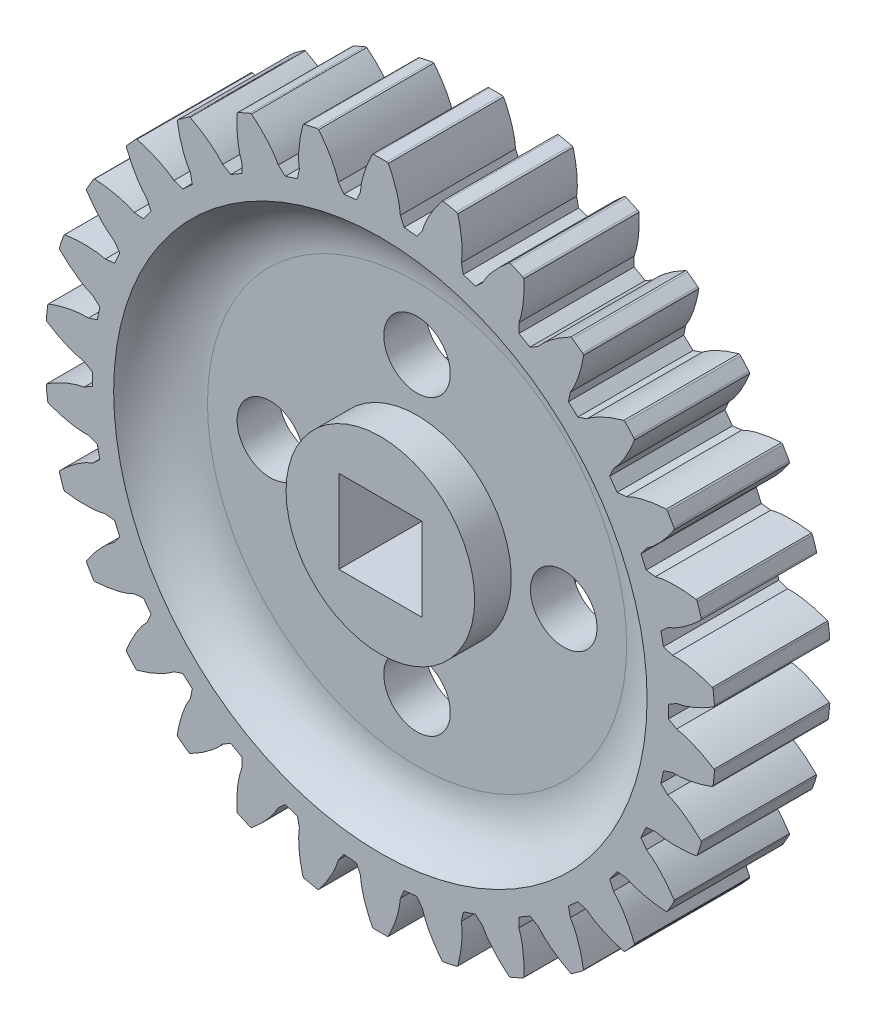
SolidWorks part; units mm, degrees
material "Nylon 101"
ref_plane "Front Plane" through (0, 0, 0) normal (0, 0, 1) x (1, 0, 0)
ref_plane "Top Plane" through (0, 0, 0) normal (0, 1, 0) x (1, 0, 0)
ref_plane "Right Plane" through (0, 0, 0) normal (1, 0, 0) x (0, 0, -1)
ref_axis "Axis1" through (0, 0, -3.2875) along (0, 0, 1)
sketch "Sketch1" plane through (0, 0, 0) normal (0, 0, 1) x (1, 0, 0)
  arc A0 (3.6196, 15.5852) -> (3.0324, 15.71) centre (0, 0) ccw
  arc A1 (0.3001, 15.9972) -> (-0.3001, 15.9972) centre (0, 0) ccw
  arc A2 (-3.0324, 15.71) -> (-3.6196, 15.5852) centre (0, 0) ccw
  arc A3 (-6.2325, 14.7362) -> (-6.7808, 14.4921) centre (0, 0) ccw
  arc A4 (-9.1601, 13.1184) -> (-9.6457, 12.7656) centre (0, 0) ccw
  arc A5 (-11.6874, 10.9272) -> (-12.089, 10.4812) centre (0, 0) ccw
  arc A6 (-13.7039, 8.2585) -> (-14.004, 7.7387) centre (0, 0) ccw
  arc A7 (-15.1215, 5.2288) -> (-15.307, 4.658) centre (0, 0) ccw
  arc A8 (-15.8782, 1.9706) -> (-15.9409, 1.3737) centre (0, 0) ccw
  arc A9 (-15.9409, -1.3737) -> (-15.8782, -1.9706) centre (0, 0) ccw
  arc A10 (-15.307, -4.658) -> (-15.1215, -5.2288) centre (0, 0) ccw
  arc A11 (-14.004, -7.7387) -> (-13.7039, -8.2585) centre (0, 0) ccw
  arc A12 (-12.089, -10.4812) -> (-11.6874, -10.9272) centre (0, 0) ccw
  arc A13 (-9.6457, -12.7656) -> (-9.1601, -13.1184) centre (0, 0) ccw
  arc A14 (-6.7808, -14.4921) -> (-6.2325, -14.7362) centre (0, 0) ccw
  arc A15 (-3.6196, -15.5852) -> (-3.0324, -15.71) centre (0, 0) ccw
  arc A16 (-0.3001, -15.9972) -> (0.3001, -15.9972) centre (0, 0) ccw
  arc A17 (3.0324, -15.71) -> (3.6196, -15.5852) centre (0, 0) ccw
  arc A18 (6.2325, -14.7362) -> (6.7808, -14.4921) centre (0, 0) ccw
  arc A19 (9.1601, -13.1184) -> (9.6457, -12.7656) centre (0, 0) ccw
  arc A20 (11.6874, -10.9272) -> (12.089, -10.4812) centre (0, 0) ccw
  arc A21 (13.7039, -8.2585) -> (14.004, -7.7387) centre (0, 0) ccw
  arc A22 (15.1215, -5.2288) -> (15.307, -4.658) centre (0, 0) ccw
  arc A23 (15.8782, -1.9706) -> (15.9409, -1.3737) centre (0, 0) ccw
  arc A24 (15.9409, 1.3737) -> (15.8782, 1.9706) centre (0, 0) ccw
  arc A25 (15.307, 4.658) -> (15.1215, 5.2288) centre (0, 0) ccw
  arc A26 (14.004, 7.7387) -> (13.7039, 8.2585) centre (0, 0) ccw
  arc A27 (12.089, 10.4812) -> (11.6874, 10.9272) centre (0, 0) ccw
  arc A28 (9.6457, 12.7656) -> (9.1601, 13.1184) centre (0, 0) ccw
  arc A29 (6.7808, 14.4921) -> (6.2325, 14.7362) centre (0, 0) ccw
  spline S0 degree 2 poles (3.6196, 15.5852) (3.6647, 15.5747) (3.6932, 15.5435) knots 0 0 0 1 1 1
  spline S1 degree 2 poles (2.9482, 15.7019) (2.9869, 15.7188) (3.0324, 15.71) knots 0 0 0 1 1 1
  spline S2 degree 2 poles (2.0027, 14.0013) (2.021, 14.0609) (2.0394, 14.1205) (2.1444, 14.4615) (2.6134, 15.2842) (2.9482, 15.7019) knots -0.082148 -0.082148 -0.082148 0 0 0.469989 0.94695 0.94695 0.94695
  spline S3 degree 2 poles (1.7379, 13.6408) (1.799, 13.7255) (1.8601, 13.8102) (1.9057, 13.8734) (1.9535, 13.9364) (1.9781, 13.9689) (2.0027, 14.0013) knots -1.340212 -1.340212 -1.340212 0 0 1 1 1.515233 1.515233 1.515233
  spline S4 degree 2 poles (1.1362, 13.7041) (1.2218, 13.6959) (1.3075, 13.6877) (1.4373, 13.6753) (1.5669, 13.6604) (1.6524, 13.6506) (1.7379, 13.6408) knots -0.659931 -0.659931 -0.659931 0 0 1 1 1.659931 1.659931 1.659931
  spline S5 degree 2 poles (0.9521, 14.1118) (0.9694, 14.0749) (0.9867, 14.038) (1.0203, 13.9665) (1.0518, 13.8952) (1.094, 13.7996) (1.1362, 13.7041) knots -0.515233 -0.515233 -0.515233 0 0 1 1 2.340212 2.340212 2.340212
  spline S6 degree 2 poles (0.3808, 15.9717) (0.7214, 15.2951) (0.9228, 14.4394) (0.941, 14.236) (0.9466, 14.1739) (0.9521, 14.1118) knots 0 0 0 0.627513 0.879079 0.879079 0.955892 0.955892 0.955892
  spline S7 degree 2 poles (0.3001, 15.9972) (0.3465, 15.9963) (0.3808, 15.9717) knots 0 0 0 1 1 1
  spline S8 degree 2 poles (-0.3808, 15.9717) (-0.3465, 15.9963) (-0.3001, 15.9972) knots 0 0 0 1 1 1
  spline S9 degree 2 poles (-0.9521, 14.1118) (-0.9466, 14.1739) (-0.941, 14.236) (-0.9092, 14.5914) (-0.6215, 15.4935) (-0.3808, 15.9717) knots -0.082148 -0.082148 -0.082148 0 0 0.469989 0.94695 0.94695 0.94695
  spline S10 degree 2 poles (-1.1362, 13.7041) (-1.094, 13.7996) (-1.0518, 13.8952) (-1.0203, 13.9665) (-0.9867, 14.038) (-0.9694, 14.0749) (-0.9521, 14.1118) knots -1.340212 -1.340212 -1.340212 0 0 1 1 1.515233 1.515233 1.515233
  spline S11 degree 2 poles (-1.7379, 13.6408) (-1.6524, 13.6506) (-1.5669, 13.6604) (-1.4373, 13.6753) (-1.3075, 13.6877) (-1.2218, 13.6959) (-1.1362, 13.7041) knots -0.659931 -0.659931 -0.659931 0 0 1 1 1.659931 1.659931 1.659931
  spline S12 degree 2 poles (-2.0027, 14.0013) (-1.9781, 13.9689) (-1.9535, 13.9364) (-1.9057, 13.8734) (-1.8601, 13.8102) (-1.799, 13.7255) (-1.7379, 13.6408) knots -0.515233 -0.515233 -0.515233 0 0 1 1 2.340212 2.340212 2.340212
  spline S13 degree 2 poles (-2.9482, 15.7019) (-2.4744, 15.1108) (-2.0995, 14.3157) (-2.0394, 14.1205) (-2.021, 14.0609) (-2.0027, 14.0013) knots 0 0 0 0.627513 0.879079 0.879079 0.955892 0.955892 0.955892
  spline S14 degree 2 poles (-3.0324, 15.71) (-2.9869, 15.7188) (-2.9482, 15.7019) knots 0 0 0 1 1 1
  spline S15 degree 2 poles (-3.6932, 15.5435) (-3.6647, 15.5747) (-3.6196, 15.5852) knots 0 0 0 1 1 1
  spline S16 degree 2 poles (-3.8653, 13.6054) (-3.8728, 13.6673) (-3.8803, 13.7292) (-3.923, 14.0835) (-3.8292, 15.0258) (-3.6932, 15.5435) knots -0.082148 -0.082148 -0.082148 0 0 0.469989 0.94695 0.94695 0.94695
  spline S17 degree 2 poles (-3.9606, 13.1684) (-3.9392, 13.2706) (-3.9178, 13.3728) (-3.9018, 13.4491) (-3.8839, 13.5261) (-3.8746, 13.5658) (-3.8653, 13.6054) knots -1.340212 -1.340212 -1.340212 0 0 1 1 1.515233 1.515233 1.515233
  spline S18 degree 2 poles (-4.536, 12.9814) (-4.4544, 13.0088) (-4.3728, 13.0361) (-4.2492, 13.0776) (-4.1248, 13.1167) (-4.0427, 13.1426) (-3.9606, 13.1684) knots -0.659931 -0.659931 -0.659931 0 0 1 1 1.659931 1.659931 1.659931
  spline S19 degree 2 poles (-4.87, 13.279) (-4.8392, 13.2524) (-4.8083, 13.2257) (-4.7485, 13.174) (-4.6908, 13.1217) (-4.6134, 13.0515) (-4.536, 12.9814) knots -0.515233 -0.515233 -0.515233 0 0 1 1 2.340212 2.340212 2.340212
  spline S20 degree 2 poles (-6.1484, 14.7458) (-5.5621, 14.2662) (-5.03, 13.5664) (-4.9306, 13.388) (-4.9003, 13.3335) (-4.87, 13.279) knots 0 0 0 0.627513 0.879079 0.879079 0.955892 0.955892 0.955892
  spline S21 degree 2 poles (-6.2325, 14.7362) (-6.1897, 14.7543) (-6.1484, 14.7458) knots 0 0 0 1 1 1
  spline S22 degree 2 poles (-6.8442, 14.436) (-6.8228, 14.4724) (-6.7808, 14.4921) knots 0 0 0 1 1 1
  spline S23 degree 2 poles (-6.6096, 12.5045) (-6.6298, 12.5635) (-6.6499, 12.6225) (-6.7654, 12.9601) (-6.8695, 13.9013) (-6.8442, 14.436) knots -0.082148 -0.082148 -0.082148 0 0 0.469989 0.94695 0.94695 0.94695
  spline S24 degree 2 poles (-6.6119, 12.0572) (-6.6122, 12.1616) (-6.6126, 12.2661) (-6.6128, 12.344) (-6.6112, 12.423) (-6.6104, 12.4637) (-6.6096, 12.5045) knots -1.340212 -1.340212 -1.340212 0 0 1 1 1.515233 1.515233 1.515233
  spline S25 degree 2 poles (-7.1359, 11.7546) (-7.0617, 11.7984) (-6.9876, 11.8421) (-6.8753, 11.9084) (-6.7618, 11.9725) (-6.6868, 12.0148) (-6.6119, 12.0572) knots -0.659931 -0.659931 -0.659931 0 0 1 1 1.659931 1.659931 1.659931
  spline S26 degree 2 poles (-7.5244, 11.9763) (-7.4887, 11.9566) (-7.453, 11.937) (-7.3838, 11.8989) (-7.3164, 11.8597) (-7.2262, 11.8072) (-7.1359, 11.7546) knots -0.515233 -0.515233 -0.515233 0 0 1 1 2.340212 2.340212 2.340212
  spline S27 degree 2 poles (-9.0799, 13.1452) (-8.4066, 12.798) (-7.7407, 12.2241) (-7.6064, 12.0703) (-7.5654, 12.0233) (-7.5244, 11.9763) knots 0 0 0 0.627513 0.879079 0.879079 0.955892 0.955892 0.955892
  spline S28 degree 2 poles (-9.1601, 13.1184) (-9.1221, 13.145) (-9.0799, 13.1452) knots 0 0 0 1 1 1
  spline S29 degree 2 poles (-9.696, 12.6976) (-9.6827, 12.7376) (-9.6457, 12.7656) knots 0 0 0 1 1 1
  spline S30 degree 2 poles (-9.065, 10.857) (-9.097, 10.9105) (-9.129, 10.964) (-9.3121, 11.2702) (-9.6097, 12.1692) (-9.696, 12.6976) knots -0.082148 -0.082148 -0.082148 0 0 0.469989 0.94695 0.94695 0.94695
  spline S31 degree 2 poles (-8.9742, 10.419) (-8.9963, 10.5211) (-9.0183, 10.6232) (-9.0348, 10.6994) (-9.0496, 10.777) (-9.0573, 10.817) (-9.065, 10.857) knots -1.340212 -1.340212 -1.340212 0 0 1 1 1.515233 1.515233 1.515233
  spline S32 degree 2 poles (-9.4239, 10.0141) (-9.3605, 10.0723) (-9.297, 10.1305) (-9.201, 10.2187) (-9.1032, 10.305) (-9.0387, 10.362) (-8.9742, 10.419) knots -0.659931 -0.659931 -0.659931 0 0 1 1 1.659931 1.659931 1.659931
  spline S33 degree 2 poles (-9.85, 10.1502) (-9.811, 10.1384) (-9.772, 10.1266) (-9.6964, 10.1037) (-9.6223, 10.0793) (-9.5231, 10.0467) (-9.4239, 10.0141) knots -0.515233 -0.515233 -0.515233 0 0 1 1 2.340212 2.340212 2.340212
  spline S34 degree 2 poles (-11.6145, 10.9702) (-10.8838, 10.7705) (-10.1131, 10.3476) (-9.9497, 10.225) (-9.8999, 10.1876) (-9.85, 10.1502) knots 0 0 0 0.627513 0.879079 0.879079 0.955892 0.955892 0.955892
  spline S35 degree 2 poles (-11.6874, 10.9272) (-11.6557, 10.9611) (-11.6145, 10.9702) knots 0 0 0 1 1 1
  spline S36 degree 2 poles (-12.1241, 10.4042) (-12.1194, 10.4461) (-12.089, 10.4812) knots 0 0 0 1 1 1
  spline S37 degree 2 poles (-11.1242, 8.735) (-11.1666, 8.7807) (-11.209, 8.8264) (-11.4519, 9.0879) (-11.9298, 9.9053) (-12.1241, 10.4042) knots -0.082148 -0.082148 -0.082148 0 0 0.469989 0.94695 0.94695 0.94695
  spline S38 degree 2 poles (-10.9443, 8.3255) (-10.9871, 8.4207) (-11.0299, 8.516) (-11.0619, 8.5871) (-11.0925, 8.66) (-11.1084, 8.6975) (-11.1242, 8.735) knots -1.340212 -1.340212 -1.340212 0 0 1 1 1.515233 1.515233 1.515233
  spline S39 degree 2 poles (-11.3, 7.836) (-11.2501, 7.9061) (-11.2001, 7.9762) (-11.1245, 8.0824) (-11.0468, 8.1872) (-10.9956, 8.2563) (-10.9443, 8.3255) knots -0.659931 -0.659931 -0.659931 0 0 1 1 1.659931 1.659931 1.659931
  spline S40 degree 2 poles (-11.7451, 7.8804) (-11.7045, 7.877) (-11.6639, 7.8736) (-11.5851, 7.8669) (-11.5077, 7.8585) (-11.4038, 7.8472) (-11.3, 7.836) knots -0.515233 -0.515233 -0.515233 0 0 1 1 2.340212 2.340212 2.340212
  spline S41 degree 2 poles (-13.6415, 8.3157) (-12.8853, 8.2723) (-12.0435, 8.0189) (-11.8582, 7.9329) (-11.8016, 7.9067) (-11.7451, 7.8804) knots 0 0 0 0.627513 0.879079 0.879079 0.955892 0.955892 0.955892
  spline S42 degree 2 poles (-13.7039, 8.2585) (-13.68, 8.2982) (-13.6415, 8.3157) knots 0 0 0 1 1 1
  spline S43 degree 2 poles (-14.0223, 7.6561) (-14.0265, 7.6981) (-14.004, 7.7387) knots 0 0 0 1 1 1
  spline S44 degree 2 poles (-12.6972, 6.2313) (-12.7482, 6.2672) (-12.7992, 6.3031) (-13.0911, 6.5083) (-13.7285, 7.2085) (-14.0223, 7.6561) knots -0.082148 -0.082148 -0.082148 0 0 0.469989 0.94695 0.94695 0.94695
  spline S45 degree 2 poles (-12.4361, 5.8681) (-12.4978, 5.9524) (-12.5595, 6.0367) (-12.6055, 6.0996) (-12.6507, 6.1645) (-12.6739, 6.1979) (-12.6972, 6.2313) knots -1.340212 -1.340212 -1.340212 0 0 1 1 1.515233 1.515233 1.515233
  spline S46 degree 2 poles (-12.6822, 5.3153) (-12.648, 5.3943) (-12.6137, 5.4732) (-12.5618, 5.5929) (-12.5076, 5.7115) (-12.4719, 5.7898) (-12.4361, 5.8681) knots -0.659931 -0.659931 -0.659931 0 0 1 1 1.659931 1.659931 1.659931
  spline S47 degree 2 poles (-13.1269, 5.2663) (-13.0864, 5.2714) (-13.046, 5.2764) (-12.9676, 5.2863) (-12.8901, 5.2942) (-12.7861, 5.3048) (-12.6822, 5.3153) knots -0.515233 -0.515233 -0.515233 0 0 1 1 2.340212 2.340212 2.340212
  spline S48 degree 2 poles (-15.0723, 5.2977) (-14.3236, 5.4125) (-13.4475, 5.3396) (-13.2484, 5.2941) (-13.1876, 5.2802) (-13.1269, 5.2663) knots 0 0 0 0.627513 0.879079 0.879079 0.955892 0.955892 0.955892
  spline S49 degree 2 poles (-15.1215, 5.2288) (-15.1063, 5.2727) (-15.0723, 5.2977) knots 0 0 0 1 1 1
  spline S50 degree 2 poles (-15.3077, 4.5734) (-15.3205, 4.6136) (-15.307, 4.658) knots 0 0 0 1 1 1
  spline S51 degree 2 poles (-13.7153, 3.4553) (-13.7727, 3.4797) (-13.83, 3.5042) (-14.1582, 3.6443) (-14.9273, 4.1967) (-15.3077, 4.5734) knots -0.082148 -0.082148 -0.082148 0 0 0.469989 0.94695 0.94695 0.94695
  spline S52 degree 2 poles (-13.3844, 3.1542) (-13.4623, 3.2239) (-13.5401, 3.2935) (-13.5982, 3.3455) (-13.6559, 3.3995) (-13.6856, 3.4274) (-13.7153, 3.4553) knots -1.340212 -1.340212 -1.340212 0 0 1 1 1.515233 1.515233 1.515233
  spline S53 degree 2 poles (-13.5102, 2.5624) (-13.4931, 2.6468) (-13.476, 2.7311) (-13.4501, 2.8589) (-13.4218, 2.9862) (-13.4031, 3.0702) (-13.3844, 3.1542) knots -0.659931 -0.659931 -0.659931 0 0 1 1 1.659931 1.659931 1.659931
  spline S54 degree 2 poles (-13.9349, 2.422) (-13.8964, 2.4353) (-13.858, 2.4487) (-13.7833, 2.4747) (-13.7091, 2.4985) (-13.6097, 2.5305) (-13.5102, 2.5624) knots -0.515233 -0.515233 -0.515233 0 0 1 1 2.340212 2.340212 2.340212
  spline S55 degree 2 poles (-15.8444, 2.0482) (-15.1359, 2.3162) (-14.2639, 2.4271) (-14.0596, 2.4239) (-13.9973, 2.4229) (-13.9349, 2.422) knots 0 0 0 0.627513 0.879079 0.879079 0.955892 0.955892 0.955892
  spline S56 degree 2 poles (-15.8782, 1.9706) (-15.8725, 2.0167) (-15.8444, 2.0482) knots 0 0 0 1 1 1
  spline S57 degree 2 poles (-15.924, 1.2908) (-15.9449, 1.3275) (-15.9409, 1.3737) knots 0 0 0 1 1 1
  spline S58 degree 2 poles (-14.134, 0.5282) (-14.1952, 0.5402) (-14.2564, 0.5522) (-14.6065, 0.621) (-15.4736, 1.0014) (-15.924, 1.2908) knots -0.082148 -0.082148 -0.082148 0 0 0.469989 0.94695 0.94695 0.94695
  spline S59 degree 2 poles (-13.7477, 0.3025) (-13.8384, 0.3545) (-13.929, 0.4064) (-13.9966, 0.4451) (-14.0643, 0.486) (-14.0991, 0.5071) (-14.134, 0.5282) knots -1.340212 -1.340212 -1.340212 0 0 1 1 1.515233 1.515233 1.515233
  spline S60 degree 2 poles (-13.7477, -0.3025) (-13.7486, -0.2165) (-13.7494, -0.1304) (-13.7506, 0) (-13.7494, 0.1304) (-13.7486, 0.2165) (-13.7477, 0.3025) knots -0.659931 -0.659931 -0.659931 0 0 1 1 1.659931 1.659931 1.659931
  spline S61 degree 2 poles (-14.134, -0.5282) (-14.0991, -0.5071) (-14.0643, -0.486) (-13.9966, -0.4451) (-13.929, -0.4064) (-13.8384, -0.3545) (-13.7477, -0.3025) knots -0.515233 -0.515233 -0.515233 0 0 1 1 2.340212 2.340212 2.340212
  spline S62 degree 2 poles (-15.924, -1.2908) (-15.2867, -0.8814) (-14.4568, -0.5916) (-14.2564, -0.5522) (-14.1952, -0.5402) (-14.134, -0.5282) knots 0 0 0 0.627513 0.879079 0.879079 0.955892 0.955892 0.955892
  spline S63 degree 2 poles (-15.9409, -1.3737) (-15.9449, -1.3275) (-15.924, -1.2908) knots 0 0 0 1 1 1
  spline S64 degree 2 poles (-15.8444, -2.0482) (-15.8725, -2.0167) (-15.8782, -1.9706) knots 0 0 0 1 1 1
  spline S65 degree 2 poles (-13.9349, -2.422) (-13.9973, -2.4229) (-14.0596, -2.4239) (-14.4164, -2.4294) (-15.3437, -2.2376) (-15.8444, -2.0482) knots -0.082148 -0.082148 -0.082148 0 0 0.469989 0.94695 0.94695 0.94695
  spline S66 degree 2 poles (-13.5102, -2.5624) (-13.6097, -2.5305) (-13.7091, -2.4985) (-13.7833, -2.4747) (-13.858, -2.4487) (-13.8964, -2.4353) (-13.9349, -2.422) knots -1.340212 -1.340212 -1.340212 0 0 1 1 1.515233 1.515233 1.515233
  spline S67 degree 2 poles (-13.3844, -3.1542) (-13.4031, -3.0702) (-13.4218, -2.9862) (-13.4501, -2.8589) (-13.476, -2.7311) (-13.4931, -2.6468) (-13.5102, -2.5624) knots -0.659931 -0.659931 -0.659931 0 0 1 1 1.659931 1.659931 1.659931
  spline S68 degree 2 poles (-13.7153, -3.4553) (-13.6856, -3.4274) (-13.6559, -3.3995) (-13.5982, -3.3455) (-13.5401, -3.2935) (-13.4623, -3.2239) (-13.3844, -3.1542) knots -0.515233 -0.515233 -0.515233 0 0 1 1 2.340212 2.340212 2.340212
  spline S69 degree 2 poles (-15.3077, -4.5734) (-14.7694, -4.0404) (-14.0179, -3.5844) (-13.83, -3.5042) (-13.7727, -3.4797) (-13.7153, -3.4553) knots 0 0 0 0.627513 0.879079 0.879079 0.955892 0.955892 0.955892
  spline S70 degree 2 poles (-15.307, -4.658) (-15.3205, -4.6136) (-15.3077, -4.5734) knots 0 0 0 1 1 1
  spline S71 degree 2 poles (-15.0723, -5.2977) (-15.1063, -5.2727) (-15.1215, -5.2288) knots 0 0 0 1 1 1
  spline S72 degree 2 poles (-13.1269, -5.2663) (-13.1876, -5.2802) (-13.2484, -5.2941) (-13.5962, -5.3737) (-14.5432, -5.3788) (-15.0723, -5.2977) knots -0.082148 -0.082148 -0.082148 0 0 0.469989 0.94695 0.94695 0.94695
  spline S73 degree 2 poles (-12.6822, -5.3153) (-12.7861, -5.3048) (-12.8901, -5.2942) (-12.9676, -5.2863) (-13.046, -5.2764) (-13.0864, -5.2714) (-13.1269, -5.2663) knots -1.340212 -1.340212 -1.340212 0 0 1 1 1.515233 1.515233 1.515233
  spline S74 degree 2 poles (-12.4361, -5.8681) (-12.4719, -5.7898) (-12.5076, -5.7115) (-12.5618, -5.5929) (-12.6137, -5.4732) (-12.648, -5.3943) (-12.6822, -5.3153) knots -0.659931 -0.659931 -0.659931 0 0 1 1 1.659931 1.659931 1.659931
  spline S75 degree 2 poles (-12.6972, -6.2313) (-12.6739, -6.1979) (-12.6507, -6.1645) (-12.6055, -6.0996) (-12.5595, -6.0367) (-12.4978, -5.9524) (-12.4361, -5.8681) knots -0.515233 -0.515233 -0.515233 0 0 1 1 2.340212 2.340212 2.340212
  spline S76 degree 2 poles (-14.0223, -7.6561) (-13.6066, -7.0228) (-12.9663, -6.4205) (-12.7992, -6.3031) (-12.7482, -6.2672) (-12.6972, -6.2313) knots 0 0 0 0.627513 0.879079 0.879079 0.955892 0.955892 0.955892
  spline S77 degree 2 poles (-14.004, -7.7387) (-14.0265, -7.6981) (-14.0223, -7.6561) knots 0 0 0 1 1 1
  spline S78 degree 2 poles (-13.6415, -8.3157) (-13.68, -8.2982) (-13.7039, -8.2585) knots 0 0 0 1 1 1
  spline S79 degree 2 poles (-11.7451, -7.8804) (-11.8016, -7.9067) (-11.8582, -7.9329) (-12.1819, -8.0831) (-13.1071, -8.285) (-13.6415, -8.3157) knots -0.082148 -0.082148 -0.082148 0 0 0.469989 0.94695 0.94695 0.94695
  spline S80 degree 2 poles (-11.3, -7.836) (-11.4038, -7.8472) (-11.5077, -7.8585) (-11.5851, -7.8669) (-11.6639, -7.8736) (-11.7045, -7.877) (-11.7451, -7.8804) knots -1.340212 -1.340212 -1.340212 0 0 1 1 1.515233 1.515233 1.515233
  spline S81 degree 2 poles (-10.9443, -8.3255) (-10.9956, -8.2563) (-11.0468, -8.1872) (-11.1245, -8.0824) (-11.2001, -7.9762) (-11.2501, -7.9061) (-11.3, -7.836) knots -0.659931 -0.659931 -0.659931 0 0 1 1 1.659931 1.659931 1.659931
  spline S82 degree 2 poles (-11.1242, -8.735) (-11.1084, -8.6975) (-11.0925, -8.66) (-11.0619, -8.5871) (-11.0299, -8.516) (-10.9871, -8.4207) (-10.9443, -8.3255) knots -0.515233 -0.515233 -0.515233 0 0 1 1 2.340212 2.340212 2.340212
  spline S83 degree 2 poles (-12.1241, -10.4042) (-11.8492, -9.6983) (-11.348, -8.9761) (-11.209, -8.8264) (-11.1666, -8.7807) (-11.1242, -8.735) knots 0 0 0 0.627513 0.879079 0.879079 0.955892 0.955892 0.955892
  spline S84 degree 2 poles (-12.089, -10.4812) (-12.1194, -10.4461) (-12.1241, -10.4042) knots 0 0 0 1 1 1
  spline S85 degree 2 poles (-11.6145, -10.9702) (-11.6557, -10.9611) (-11.6874, -10.9272) knots 0 0 0 1 1 1
  spline S86 degree 2 poles (-9.85, -10.1502) (-9.8999, -10.1876) (-9.9497, -10.225) (-10.2351, -10.4392) (-11.0981, -10.8291) (-11.6145, -10.9702) knots -0.082148 -0.082148 -0.082148 0 0 0.469989 0.94695 0.94695 0.94695
  spline S87 degree 2 poles (-9.4239, -10.0141) (-9.5231, -10.0467) (-9.6223, -10.0793) (-9.6964, -10.1037) (-9.772, -10.1266) (-9.811, -10.1384) (-9.85, -10.1502) knots -1.340212 -1.340212 -1.340212 0 0 1 1 1.515233 1.515233 1.515233
  spline S88 degree 2 poles (-8.9742, -10.419) (-9.0387, -10.362) (-9.1032, -10.305) (-9.201, -10.2187) (-9.297, -10.1305) (-9.3605, -10.0723) (-9.4239, -10.0141) knots -0.659931 -0.659931 -0.659931 0 0 1 1 1.659931 1.659931 1.659931
  spline S89 degree 2 poles (-9.065, -10.857) (-9.0573, -10.817) (-9.0496, -10.777) (-9.0348, -10.6994) (-9.0183, -10.6232) (-8.9963, -10.5211) (-8.9742, -10.419) knots -0.515233 -0.515233 -0.515233 0 0 1 1 2.340212 2.340212 2.340212
  spline S90 degree 2 poles (-9.696, -12.6976) (-9.5738, -11.95) (-9.2338, -11.1393) (-9.129, -10.964) (-9.097, -10.9105) (-9.065, -10.857) knots 0 0 0 0.627513 0.879079 0.879079 0.955892 0.955892 0.955892
  spline S91 degree 2 poles (-9.6457, -12.7656) (-9.6827, -12.7376) (-9.696, -12.6976) knots 0 0 0 1 1 1
  spline S92 degree 2 poles (-9.0799, -13.1452) (-9.1221, -13.145) (-9.1601, -13.1184) knots 0 0 0 1 1 1
  spline S93 degree 2 poles (-7.5244, -11.9763) (-7.5654, -12.0233) (-7.6064, -12.0703) (-7.841, -12.3391) (-8.6041, -12.8998) (-9.0799, -13.1452) knots -0.082148 -0.082148 -0.082148 0 0 0.469989 0.94695 0.94695 0.94695
  spline S94 degree 2 poles (-7.1359, -11.7546) (-7.2262, -11.8072) (-7.3164, -11.8597) (-7.3838, -11.8989) (-7.453, -11.937) (-7.4887, -11.9566) (-7.5244, -11.9763) knots -1.340212 -1.340212 -1.340212 0 0 1 1 1.515233 1.515233 1.515233
  spline S95 degree 2 poles (-6.6119, -12.0572) (-6.6868, -12.0148) (-6.7618, -11.9725) (-6.8753, -11.9084) (-6.9876, -11.8421) (-7.0617, -11.7984) (-7.1359, -11.7546) knots -0.659931 -0.659931 -0.659931 0 0 1 1 1.659931 1.659931 1.659931
  spline S96 degree 2 poles (-6.6096, -12.5045) (-6.6104, -12.4637) (-6.6112, -12.423) (-6.6128, -12.344) (-6.6126, -12.2661) (-6.6122, -12.1616) (-6.6119, -12.0572) knots -0.515233 -0.515233 -0.515233 0 0 1 1 2.340212 2.340212 2.340212
  spline S97 degree 2 poles (-6.8442, -14.436) (-6.8801, -13.6794) (-6.716, -12.8157) (-6.6499, -12.6225) (-6.6298, -12.5635) (-6.6096, -12.5045) knots 0 0 0 0.627513 0.879079 0.879079 0.955892 0.955892 0.955892
  spline S98 degree 2 poles (-6.7808, -14.4921) (-6.8228, -14.4724) (-6.8442, -14.436) knots 0 0 0 1 1 1
  spline S99 degree 2 poles (-6.1484, -14.7458) (-6.1897, -14.7543) (-6.2325, -14.7362) knots 0 0 0 1 1 1
  spline S100 degree 2 poles (-4.87, -13.279) (-4.9003, -13.3335) (-4.9306, -13.388) (-5.1043, -13.6997) (-5.734, -14.4068) (-6.1484, -14.7458) knots -0.082148 -0.082148 -0.082148 0 0 0.469989 0.94695 0.94695 0.94695
  spline S101 degree 2 poles (-4.536, -12.9814) (-4.6134, -13.0515) (-4.6908, -13.1217) (-4.7485, -13.174) (-4.8083, -13.2257) (-4.8392, -13.2524) (-4.87, -13.279) knots -1.340212 -1.340212 -1.340212 0 0 1 1 1.515233 1.515233 1.515233
  spline S102 degree 2 poles (-3.9606, -13.1684) (-4.0427, -13.1426) (-4.1248, -13.1167) (-4.2492, -13.0776) (-4.3728, -13.0361) (-4.4544, -13.0088) (-4.536, -12.9814) knots -0.659931 -0.659931 -0.659931 0 0 1 1 1.659931 1.659931 1.659931
  spline S103 degree 2 poles (-3.8653, -13.6054) (-3.8746, -13.5658) (-3.8839, -13.5261) (-3.9018, -13.4491) (-3.9178, -13.3728) (-3.9392, -13.2706) (-3.9606, -13.1684) knots -0.515233 -0.515233 -0.515233 0 0 1 1 2.340212 2.340212 2.340212
  spline S104 degree 2 poles (-3.6932, -15.5435) (-3.8856, -14.8109) (-3.9047, -13.932) (-3.8803, -13.7292) (-3.8728, -13.6673) (-3.8653, -13.6054) knots 0 0 0 0.627513 0.879079 0.879079 0.955892 0.955892 0.955892
  spline S105 degree 2 poles (-3.6196, -15.5852) (-3.6647, -15.5747) (-3.6932, -15.5435) knots 0 0 0 1 1 1
  spline S106 degree 2 poles (-2.9482, -15.7019) (-2.9869, -15.7188) (-3.0324, -15.71) knots 0 0 0 1 1 1
  spline S107 degree 2 poles (-2.0027, -14.0013) (-2.021, -14.0609) (-2.0394, -14.1205) (-2.1444, -14.4615) (-2.6134, -15.2842) (-2.9482, -15.7019) knots -0.082148 -0.082148 -0.082148 0 0 0.469989 0.94695 0.94695 0.94695
  spline S108 degree 2 poles (-1.7379, -13.6408) (-1.799, -13.7255) (-1.8601, -13.8102) (-1.9057, -13.8734) (-1.9535, -13.9364) (-1.9781, -13.9689) (-2.0027, -14.0013) knots -1.340212 -1.340212 -1.340212 0 0 1 1 1.515233 1.515233 1.515233
  spline S109 degree 2 poles (-1.1362, -13.7041) (-1.2218, -13.6959) (-1.3075, -13.6877) (-1.4373, -13.6753) (-1.5669, -13.6604) (-1.6524, -13.6506) (-1.7379, -13.6408) knots -0.659931 -0.659931 -0.659931 0 0 1 1 1.659931 1.659931 1.659931
  spline S110 degree 2 poles (-0.9521, -14.1118) (-0.9694, -14.0749) (-0.9867, -14.038) (-1.0203, -13.9665) (-1.0518, -13.8952) (-1.094, -13.7996) (-1.1362, -13.7041) knots -0.515233 -0.515233 -0.515233 0 0 1 1 2.340212 2.340212 2.340212
  spline S111 degree 2 poles (-0.3808, -15.9717) (-0.7214, -15.2951) (-0.9228, -14.4394) (-0.941, -14.236) (-0.9466, -14.1739) (-0.9521, -14.1118) knots 0 0 0 0.627513 0.879079 0.879079 0.955892 0.955892 0.955892
  spline S112 degree 2 poles (-0.3001, -15.9972) (-0.3465, -15.9963) (-0.3808, -15.9717) knots 0 0 0 1 1 1
  spline S113 degree 2 poles (0.3808, -15.9717) (0.3465, -15.9963) (0.3001, -15.9972) knots 0 0 0 1 1 1
  spline S114 degree 2 poles (0.9521, -14.1118) (0.9466, -14.1739) (0.941, -14.236) (0.9092, -14.5914) (0.6215, -15.4935) (0.3808, -15.9717) knots -0.082148 -0.082148 -0.082148 0 0 0.469989 0.94695 0.94695 0.94695
  spline S115 degree 2 poles (1.1362, -13.7041) (1.094, -13.7996) (1.0518, -13.8952) (1.0203, -13.9665) (0.9867, -14.038) (0.9694, -14.0749) (0.9521, -14.1118) knots -1.340212 -1.340212 -1.340212 0 0 1 1 1.515233 1.515233 1.515233
  spline S116 degree 2 poles (1.7379, -13.6408) (1.6524, -13.6506) (1.5669, -13.6604) (1.4373, -13.6753) (1.3075, -13.6877) (1.2218, -13.6959) (1.1362, -13.7041) knots -0.659931 -0.659931 -0.659931 0 0 1 1 1.659931 1.659931 1.659931
  spline S117 degree 2 poles (2.0027, -14.0013) (1.9781, -13.9689) (1.9535, -13.9364) (1.9057, -13.8734) (1.8601, -13.8102) (1.799, -13.7255) (1.7379, -13.6408) knots -0.515233 -0.515233 -0.515233 0 0 1 1 2.340212 2.340212 2.340212
  spline S118 degree 2 poles (2.9482, -15.7019) (2.4744, -15.1108) (2.0995, -14.3157) (2.0394, -14.1205) (2.021, -14.0609) (2.0027, -14.0013) knots 0 0 0 0.627513 0.879079 0.879079 0.955892 0.955892 0.955892
  spline S119 degree 2 poles (3.0324, -15.71) (2.9869, -15.7188) (2.9482, -15.7019) knots 0 0 0 1 1 1
  spline S120 degree 2 poles (3.6932, -15.5435) (3.6647, -15.5747) (3.6196, -15.5852) knots 0 0 0 1 1 1
  spline S121 degree 2 poles (3.8653, -13.6054) (3.8728, -13.6673) (3.8803, -13.7292) (3.923, -14.0835) (3.8292, -15.0258) (3.6932, -15.5435) knots -0.082148 -0.082148 -0.082148 0 0 0.469989 0.94695 0.94695 0.94695
  spline S122 degree 2 poles (3.9606, -13.1684) (3.9392, -13.2706) (3.9178, -13.3728) (3.9018, -13.4491) (3.8839, -13.5261) (3.8746, -13.5658) (3.8653, -13.6054) knots -1.340212 -1.340212 -1.340212 0 0 1 1 1.515233 1.515233 1.515233
  spline S123 degree 2 poles (4.536, -12.9814) (4.4544, -13.0088) (4.3728, -13.0361) (4.2492, -13.0776) (4.1248, -13.1167) (4.0427, -13.1426) (3.9606, -13.1684) knots -0.659931 -0.659931 -0.659931 0 0 1 1 1.659931 1.659931 1.659931
  spline S124 degree 2 poles (4.87, -13.279) (4.8392, -13.2524) (4.8083, -13.2257) (4.7485, -13.174) (4.6908, -13.1217) (4.6134, -13.0515) (4.536, -12.9814) knots -0.515233 -0.515233 -0.515233 0 0 1 1 2.340212 2.340212 2.340212
  spline S125 degree 2 poles (6.1484, -14.7458) (5.5621, -14.2662) (5.03, -13.5664) (4.9306, -13.388) (4.9003, -13.3335) (4.87, -13.279) knots 0 0 0 0.627513 0.879079 0.879079 0.955892 0.955892 0.955892
  spline S126 degree 2 poles (6.2325, -14.7362) (6.1897, -14.7543) (6.1484, -14.7458) knots 0 0 0 1 1 1
  spline S127 degree 2 poles (6.8442, -14.436) (6.8228, -14.4724) (6.7808, -14.4921) knots 0 0 0 1 1 1
  spline S128 degree 2 poles (6.6096, -12.5045) (6.6298, -12.5635) (6.6499, -12.6225) (6.7654, -12.9601) (6.8695, -13.9013) (6.8442, -14.436) knots -0.082148 -0.082148 -0.082148 0 0 0.469989 0.94695 0.94695 0.94695
  spline S129 degree 2 poles (6.6119, -12.0572) (6.6122, -12.1616) (6.6126, -12.2661) (6.6128, -12.344) (6.6112, -12.423) (6.6104, -12.4637) (6.6096, -12.5045) knots -1.340212 -1.340212 -1.340212 0 0 1 1 1.515233 1.515233 1.515233
  spline S130 degree 2 poles (7.1359, -11.7546) (7.0617, -11.7984) (6.9876, -11.8421) (6.8753, -11.9084) (6.7618, -11.9725) (6.6868, -12.0148) (6.6119, -12.0572) knots -0.659931 -0.659931 -0.659931 0 0 1 1 1.659931 1.659931 1.659931
  spline S131 degree 2 poles (7.5244, -11.9763) (7.4887, -11.9566) (7.453, -11.937) (7.3838, -11.8989) (7.3164, -11.8597) (7.2262, -11.8072) (7.1359, -11.7546) knots -0.515233 -0.515233 -0.515233 0 0 1 1 2.340212 2.340212 2.340212
  spline S132 degree 2 poles (9.0799, -13.1452) (8.4066, -12.798) (7.7407, -12.2241) (7.6064, -12.0703) (7.5654, -12.0233) (7.5244, -11.9763) knots 0 0 0 0.627513 0.879079 0.879079 0.955892 0.955892 0.955892
  spline S133 degree 2 poles (9.1601, -13.1184) (9.1221, -13.145) (9.0799, -13.1452) knots 0 0 0 1 1 1
  spline S134 degree 2 poles (9.696, -12.6976) (9.6827, -12.7376) (9.6457, -12.7656) knots 0 0 0 1 1 1
  spline S135 degree 2 poles (9.065, -10.857) (9.097, -10.9105) (9.129, -10.964) (9.3121, -11.2702) (9.6097, -12.1692) (9.696, -12.6976) knots -0.082148 -0.082148 -0.082148 0 0 0.469989 0.94695 0.94695 0.94695
  spline S136 degree 2 poles (8.9742, -10.419) (8.9963, -10.5211) (9.0183, -10.6232) (9.0348, -10.6994) (9.0496, -10.777) (9.0573, -10.817) (9.065, -10.857) knots -1.340212 -1.340212 -1.340212 0 0 1 1 1.515233 1.515233 1.515233
  spline S137 degree 2 poles (9.4239, -10.0141) (9.3605, -10.0723) (9.297, -10.1305) (9.201, -10.2187) (9.1032, -10.305) (9.0387, -10.362) (8.9742, -10.419) knots -0.659931 -0.659931 -0.659931 0 0 1 1 1.659931 1.659931 1.659931
  spline S138 degree 2 poles (9.85, -10.1502) (9.811, -10.1384) (9.772, -10.1266) (9.6964, -10.1037) (9.6223, -10.0793) (9.5231, -10.0467) (9.4239, -10.0141) knots -0.515233 -0.515233 -0.515233 0 0 1 1 2.340212 2.340212 2.340212
  spline S139 degree 2 poles (11.6145, -10.9702) (10.8838, -10.7705) (10.1131, -10.3476) (9.9497, -10.225) (9.8999, -10.1876) (9.85, -10.1502) knots 0 0 0 0.627513 0.879079 0.879079 0.955892 0.955892 0.955892
  spline S140 degree 2 poles (11.6874, -10.9272) (11.6557, -10.9611) (11.6145, -10.9702) knots 0 0 0 1 1 1
  spline S141 degree 2 poles (12.1241, -10.4042) (12.1194, -10.4461) (12.089, -10.4812) knots 0 0 0 1 1 1
  spline S142 degree 2 poles (11.1242, -8.735) (11.1666, -8.7807) (11.209, -8.8264) (11.4519, -9.0879) (11.9298, -9.9053) (12.1241, -10.4042) knots -0.082148 -0.082148 -0.082148 0 0 0.469989 0.94695 0.94695 0.94695
  spline S143 degree 2 poles (10.9443, -8.3255) (10.9871, -8.4207) (11.0299, -8.516) (11.0619, -8.5871) (11.0925, -8.66) (11.1084, -8.6975) (11.1242, -8.735) knots -1.340212 -1.340212 -1.340212 0 0 1 1 1.515233 1.515233 1.515233
  spline S144 degree 2 poles (11.3, -7.836) (11.2501, -7.9061) (11.2001, -7.9762) (11.1245, -8.0824) (11.0468, -8.1872) (10.9956, -8.2563) (10.9443, -8.3255) knots -0.659931 -0.659931 -0.659931 0 0 1 1 1.659931 1.659931 1.659931
  spline S145 degree 2 poles (11.7451, -7.8804) (11.7045, -7.877) (11.6639, -7.8736) (11.5851, -7.8669) (11.5077, -7.8585) (11.4038, -7.8472) (11.3, -7.836) knots -0.515233 -0.515233 -0.515233 0 0 1 1 2.340212 2.340212 2.340212
  spline S146 degree 2 poles (13.6415, -8.3157) (12.8853, -8.2723) (12.0435, -8.0189) (11.8582, -7.9329) (11.8016, -7.9067) (11.7451, -7.8804) knots 0 0 0 0.627513 0.879079 0.879079 0.955892 0.955892 0.955892
  spline S147 degree 2 poles (13.7039, -8.2585) (13.68, -8.2982) (13.6415, -8.3157) knots 0 0 0 1 1 1
  spline S148 degree 2 poles (14.0223, -7.6561) (14.0265, -7.6981) (14.004, -7.7387) knots 0 0 0 1 1 1
  spline S149 degree 2 poles (12.6972, -6.2313) (12.7482, -6.2672) (12.7992, -6.3031) (13.0911, -6.5083) (13.7285, -7.2085) (14.0223, -7.6561) knots -0.082148 -0.082148 -0.082148 0 0 0.469989 0.94695 0.94695 0.94695
  spline S150 degree 2 poles (12.4361, -5.8681) (12.4978, -5.9524) (12.5595, -6.0367) (12.6055, -6.0996) (12.6507, -6.1645) (12.6739, -6.1979) (12.6972, -6.2313) knots -1.340212 -1.340212 -1.340212 0 0 1 1 1.515233 1.515233 1.515233
  spline S151 degree 2 poles (12.6822, -5.3153) (12.648, -5.3943) (12.6137, -5.4732) (12.5618, -5.5929) (12.5076, -5.7115) (12.4719, -5.7898) (12.4361, -5.8681) knots -0.659931 -0.659931 -0.659931 0 0 1 1 1.659931 1.659931 1.659931
  spline S152 degree 2 poles (13.1269, -5.2663) (13.0864, -5.2714) (13.046, -5.2764) (12.9676, -5.2863) (12.8901, -5.2942) (12.7861, -5.3048) (12.6822, -5.3153) knots -0.515233 -0.515233 -0.515233 0 0 1 1 2.340212 2.340212 2.340212
  spline S153 degree 2 poles (15.0723, -5.2977) (14.3236, -5.4125) (13.4475, -5.3396) (13.2484, -5.2941) (13.1876, -5.2802) (13.1269, -5.2663) knots 0 0 0 0.627513 0.879079 0.879079 0.955892 0.955892 0.955892
  spline S154 degree 2 poles (15.1215, -5.2288) (15.1063, -5.2727) (15.0723, -5.2977) knots 0 0 0 1 1 1
  spline S155 degree 2 poles (15.3077, -4.5734) (15.3205, -4.6136) (15.307, -4.658) knots 0 0 0 1 1 1
  spline S156 degree 2 poles (13.7153, -3.4553) (13.7727, -3.4797) (13.83, -3.5042) (14.1582, -3.6443) (14.9273, -4.1967) (15.3077, -4.5734) knots -0.082148 -0.082148 -0.082148 0 0 0.469989 0.94695 0.94695 0.94695
  spline S157 degree 2 poles (13.3844, -3.1542) (13.4623, -3.2239) (13.5401, -3.2935) (13.5982, -3.3455) (13.6559, -3.3995) (13.6856, -3.4274) (13.7153, -3.4553) knots -1.340212 -1.340212 -1.340212 0 0 1 1 1.515233 1.515233 1.515233
  spline S158 degree 2 poles (13.5102, -2.5624) (13.4931, -2.6468) (13.476, -2.7311) (13.4501, -2.8589) (13.4218, -2.9862) (13.4031, -3.0702) (13.3844, -3.1542) knots -0.659931 -0.659931 -0.659931 0 0 1 1 1.659931 1.659931 1.659931
  spline S159 degree 2 poles (13.9349, -2.422) (13.8964, -2.4353) (13.858, -2.4487) (13.7833, -2.4747) (13.7091, -2.4985) (13.6097, -2.5305) (13.5102, -2.5624) knots -0.515233 -0.515233 -0.515233 0 0 1 1 2.340212 2.340212 2.340212
  spline S160 degree 2 poles (15.8444, -2.0482) (15.1359, -2.3162) (14.2639, -2.4271) (14.0596, -2.4239) (13.9973, -2.4229) (13.9349, -2.422) knots 0 0 0 0.627513 0.879079 0.879079 0.955892 0.955892 0.955892
  spline S161 degree 2 poles (15.8782, -1.9706) (15.8725, -2.0167) (15.8444, -2.0482) knots 0 0 0 1 1 1
  spline S162 degree 2 poles (15.924, -1.2908) (15.9449, -1.3275) (15.9409, -1.3737) knots 0 0 0 1 1 1
  spline S163 degree 2 poles (14.134, -0.5282) (14.1952, -0.5402) (14.2564, -0.5522) (14.6065, -0.621) (15.4736, -1.0014) (15.924, -1.2908) knots -0.082148 -0.082148 -0.082148 0 0 0.469989 0.94695 0.94695 0.94695
  spline S164 degree 2 poles (13.7477, -0.3025) (13.8384, -0.3545) (13.929, -0.4064) (13.9966, -0.4451) (14.0643, -0.486) (14.0991, -0.5071) (14.134, -0.5282) knots -1.340212 -1.340212 -1.340212 0 0 1 1 1.515233 1.515233 1.515233
  spline S165 degree 2 poles (13.7477, 0.3025) (13.7486, 0.2165) (13.7494, 0.1304) (13.7506, 0) (13.7494, -0.1304) (13.7486, -0.2165) (13.7477, -0.3025) knots -0.659931 -0.659931 -0.659931 0 0 1 1 1.659931 1.659931 1.659931
  spline S166 degree 2 poles (14.134, 0.5282) (14.0991, 0.5071) (14.0643, 0.486) (13.9966, 0.4451) (13.929, 0.4064) (13.8384, 0.3545) (13.7477, 0.3025) knots -0.515233 -0.515233 -0.515233 0 0 1 1 2.340212 2.340212 2.340212
  spline S167 degree 2 poles (15.924, 1.2908) (15.2867, 0.8814) (14.4568, 0.5916) (14.2564, 0.5522) (14.1952, 0.5402) (14.134, 0.5282) knots 0 0 0 0.627513 0.879079 0.879079 0.955892 0.955892 0.955892
  spline S168 degree 2 poles (15.9409, 1.3737) (15.9449, 1.3275) (15.924, 1.2908) knots 0 0 0 1 1 1
  spline S169 degree 2 poles (15.8444, 2.0482) (15.8725, 2.0167) (15.8782, 1.9706) knots 0 0 0 1 1 1
  spline S170 degree 2 poles (13.9349, 2.422) (13.9973, 2.4229) (14.0596, 2.4239) (14.4164, 2.4294) (15.3437, 2.2376) (15.8444, 2.0482) knots -0.082148 -0.082148 -0.082148 0 0 0.469989 0.94695 0.94695 0.94695
  spline S171 degree 2 poles (13.5102, 2.5624) (13.6097, 2.5305) (13.7091, 2.4985) (13.7833, 2.4747) (13.858, 2.4487) (13.8964, 2.4353) (13.9349, 2.422) knots -1.340212 -1.340212 -1.340212 0 0 1 1 1.515233 1.515233 1.515233
  spline S172 degree 2 poles (13.3844, 3.1542) (13.4031, 3.0702) (13.4218, 2.9862) (13.4501, 2.8589) (13.476, 2.7311) (13.4931, 2.6468) (13.5102, 2.5624) knots -0.659931 -0.659931 -0.659931 0 0 1 1 1.659931 1.659931 1.659931
  spline S173 degree 2 poles (13.7153, 3.4553) (13.6856, 3.4274) (13.6559, 3.3995) (13.5982, 3.3455) (13.5401, 3.2935) (13.4623, 3.2239) (13.3844, 3.1542) knots -0.515233 -0.515233 -0.515233 0 0 1 1 2.340212 2.340212 2.340212
  spline S174 degree 2 poles (15.3077, 4.5734) (14.7694, 4.0404) (14.0179, 3.5844) (13.83, 3.5042) (13.7727, 3.4797) (13.7153, 3.4553) knots 0 0 0 0.627513 0.879079 0.879079 0.955892 0.955892 0.955892
  spline S175 degree 2 poles (15.307, 4.658) (15.3205, 4.6136) (15.3077, 4.5734) knots 0 0 0 1 1 1
  spline S176 degree 2 poles (15.0723, 5.2977) (15.1063, 5.2727) (15.1215, 5.2288) knots 0 0 0 1 1 1
  spline S177 degree 2 poles (13.1269, 5.2663) (13.1876, 5.2802) (13.2484, 5.2941) (13.5962, 5.3737) (14.5432, 5.3788) (15.0723, 5.2977) knots -0.082148 -0.082148 -0.082148 0 0 0.469989 0.94695 0.94695 0.94695
  spline S178 degree 2 poles (12.6822, 5.3153) (12.7861, 5.3048) (12.8901, 5.2942) (12.9676, 5.2863) (13.046, 5.2764) (13.0864, 5.2714) (13.1269, 5.2663) knots -1.340212 -1.340212 -1.340212 0 0 1 1 1.515233 1.515233 1.515233
  spline S179 degree 2 poles (12.4361, 5.8681) (12.4719, 5.7898) (12.5076, 5.7115) (12.5618, 5.5929) (12.6137, 5.4732) (12.648, 5.3943) (12.6822, 5.3153) knots -0.659931 -0.659931 -0.659931 0 0 1 1 1.659931 1.659931 1.659931
  spline S180 degree 2 poles (12.6972, 6.2313) (12.6739, 6.1979) (12.6507, 6.1645) (12.6055, 6.0996) (12.5595, 6.0367) (12.4978, 5.9524) (12.4361, 5.8681) knots -0.515233 -0.515233 -0.515233 0 0 1 1 2.340212 2.340212 2.340212
  spline S181 degree 2 poles (14.0223, 7.6561) (13.6066, 7.0228) (12.9663, 6.4205) (12.7992, 6.3031) (12.7482, 6.2672) (12.6972, 6.2313) knots 0 0 0 0.627513 0.879079 0.879079 0.955892 0.955892 0.955892
  spline S182 degree 2 poles (14.004, 7.7387) (14.0265, 7.6981) (14.0223, 7.6561) knots 0 0 0 1 1 1
  spline S183 degree 2 poles (13.6415, 8.3157) (13.68, 8.2982) (13.7039, 8.2585) knots 0 0 0 1 1 1
  spline S184 degree 2 poles (11.7451, 7.8804) (11.8016, 7.9067) (11.8582, 7.9329) (12.1819, 8.0831) (13.1071, 8.285) (13.6415, 8.3157) knots -0.082148 -0.082148 -0.082148 0 0 0.469989 0.94695 0.94695 0.94695
  spline S185 degree 2 poles (11.3, 7.836) (11.4038, 7.8472) (11.5077, 7.8585) (11.5851, 7.8669) (11.6639, 7.8736) (11.7045, 7.877) (11.7451, 7.8804) knots -1.340212 -1.340212 -1.340212 0 0 1 1 1.515233 1.515233 1.515233
  spline S186 degree 2 poles (10.9443, 8.3255) (10.9956, 8.2563) (11.0468, 8.1872) (11.1245, 8.0824) (11.2001, 7.9762) (11.2501, 7.9061) (11.3, 7.836) knots -0.659931 -0.659931 -0.659931 0 0 1 1 1.659931 1.659931 1.659931
  spline S187 degree 2 poles (11.1242, 8.735) (11.1084, 8.6975) (11.0925, 8.66) (11.0619, 8.5871) (11.0299, 8.516) (10.9871, 8.4207) (10.9443, 8.3255) knots -0.515233 -0.515233 -0.515233 0 0 1 1 2.340212 2.340212 2.340212
  spline S188 degree 2 poles (12.1241, 10.4042) (11.8492, 9.6983) (11.348, 8.9761) (11.209, 8.8264) (11.1666, 8.7807) (11.1242, 8.735) knots 0 0 0 0.627513 0.879079 0.879079 0.955892 0.955892 0.955892
  spline S189 degree 2 poles (12.089, 10.4812) (12.1194, 10.4461) (12.1241, 10.4042) knots 0 0 0 1 1 1
  spline S190 degree 2 poles (11.6145, 10.9702) (11.6557, 10.9611) (11.6874, 10.9272) knots 0 0 0 1 1 1
  spline S191 degree 2 poles (9.85, 10.1502) (9.8999, 10.1876) (9.9497, 10.225) (10.2351, 10.4392) (11.0981, 10.8291) (11.6145, 10.9702) knots -0.082148 -0.082148 -0.082148 0 0 0.469989 0.94695 0.94695 0.94695
  spline S192 degree 2 poles (9.4239, 10.0141) (9.5231, 10.0467) (9.6223, 10.0793) (9.6964, 10.1037) (9.772, 10.1266) (9.811, 10.1384) (9.85, 10.1502) knots -1.340212 -1.340212 -1.340212 0 0 1 1 1.515233 1.515233 1.515233
  spline S193 degree 2 poles (8.9742, 10.419) (9.0387, 10.362) (9.1032, 10.305) (9.201, 10.2187) (9.297, 10.1305) (9.3605, 10.0723) (9.4239, 10.0141) knots -0.659931 -0.659931 -0.659931 0 0 1 1 1.659931 1.659931 1.659931
  spline S194 degree 2 poles (9.065, 10.857) (9.0573, 10.817) (9.0496, 10.777) (9.0348, 10.6994) (9.0183, 10.6232) (8.9963, 10.5211) (8.9742, 10.419) knots -0.515233 -0.515233 -0.515233 0 0 1 1 2.340212 2.340212 2.340212
  spline S195 degree 2 poles (9.696, 12.6976) (9.5738, 11.95) (9.2338, 11.1393) (9.129, 10.964) (9.097, 10.9105) (9.065, 10.857) knots 0 0 0 0.627513 0.879079 0.879079 0.955892 0.955892 0.955892
  spline S196 degree 2 poles (9.6457, 12.7656) (9.6827, 12.7376) (9.696, 12.6976) knots 0 0 0 1 1 1
  spline S197 degree 2 poles (9.0799, 13.1452) (9.1221, 13.145) (9.1601, 13.1184) knots 0 0 0 1 1 1
  spline S198 degree 2 poles (7.5244, 11.9763) (7.5654, 12.0233) (7.6064, 12.0703) (7.841, 12.3391) (8.6041, 12.8998) (9.0799, 13.1452) knots -0.082148 -0.082148 -0.082148 0 0 0.469989 0.94695 0.94695 0.94695
  spline S199 degree 2 poles (7.1359, 11.7546) (7.2262, 11.8072) (7.3164, 11.8597) (7.3838, 11.8989) (7.453, 11.937) (7.4887, 11.9566) (7.5244, 11.9763) knots -1.340212 -1.340212 -1.340212 0 0 1 1 1.515233 1.515233 1.515233
  spline S200 degree 2 poles (6.6119, 12.0572) (6.6868, 12.0148) (6.7618, 11.9725) (6.8753, 11.9084) (6.9876, 11.8421) (7.0617, 11.7984) (7.1359, 11.7546) knots -0.659931 -0.659931 -0.659931 0 0 1 1 1.659931 1.659931 1.659931
  spline S201 degree 2 poles (6.6096, 12.5045) (6.6104, 12.4637) (6.6112, 12.423) (6.6128, 12.344) (6.6126, 12.2661) (6.6122, 12.1616) (6.6119, 12.0572) knots -0.515233 -0.515233 -0.515233 0 0 1 1 2.340212 2.340212 2.340212
  spline S202 degree 2 poles (6.8442, 14.436) (6.8801, 13.6794) (6.716, 12.8157) (6.6499, 12.6225) (6.6298, 12.5635) (6.6096, 12.5045) knots 0 0 0 0.627513 0.879079 0.879079 0.955892 0.955892 0.955892
  spline S203 degree 2 poles (6.7808, 14.4921) (6.8228, 14.4724) (6.8442, 14.436) knots 0 0 0 1 1 1
  spline S204 degree 2 poles (6.1484, 14.7458) (6.1897, 14.7543) (6.2325, 14.7362) knots 0 0 0 1 1 1
  spline S205 degree 2 poles (4.87, 13.279) (4.9003, 13.3335) (4.9306, 13.388) (5.1043, 13.6997) (5.734, 14.4068) (6.1484, 14.7458) knots -0.082148 -0.082148 -0.082148 0 0 0.469989 0.94695 0.94695 0.94695
  spline S206 degree 2 poles (4.536, 12.9814) (4.6134, 13.0515) (4.6908, 13.1217) (4.7485, 13.174) (4.8083, 13.2257) (4.8392, 13.2524) (4.87, 13.279) knots -1.340212 -1.340212 -1.340212 0 0 1 1 1.515233 1.515233 1.515233
  spline S207 degree 2 poles (3.9606, 13.1684) (4.0427, 13.1426) (4.1248, 13.1167) (4.2492, 13.0776) (4.3728, 13.0361) (4.4544, 13.0088) (4.536, 12.9814) knots -0.659931 -0.659931 -0.659931 0 0 1 1 1.659931 1.659931 1.659931
  spline S208 degree 2 poles (3.8653, 13.6054) (3.8746, 13.5658) (3.8839, 13.5261) (3.9018, 13.4491) (3.9178, 13.3728) (3.9392, 13.2706) (3.9606, 13.1684) knots -0.515233 -0.515233 -0.515233 0 0 1 1 2.340212 2.340212 2.340212
  spline S209 degree 2 poles (3.6932, 15.5435) (3.8856, 14.8109) (3.9047, 13.932) (3.8803, 13.7292) (3.8728, 13.6673) (3.8653, 13.6054) knots 0 0 0 0.627513 0.879079 0.879079 0.955892 0.955892 0.955892
extrude "Boss-Extrude1" add sketch "Sketch1" against normal mid plane 5.5
sketch "Sketch5" plane through (0, 0, 0) normal (1, 0, 0) x (0, 0, -1)
  line L0 (1, 4.5) -> (3, 4.5)
  line L1 (1, 4.5) -> (1, 10)
  line L2 (3, 4.5) -> (3, 12.8284)
  arc A0 (1, 10) -> (3, 12.8284) centre (4, 10) cw
  dimension "D4" = 3
  dimension "D1" = 4.5
  dimension "D2" = 1
  dimension "D3" = 2
  dimension "D5" = 10
revolve "Cut-Revolve1" cut sketch "Sketch5" angle 360 about axis through (0, 0, -3.2875) along (0, 0, 1)
mirror "Mirror1" about plane through (0, 0, 0) normal (0, 0, 1) of "Cut-Revolve1"
hole_wizard "1/8 (0.125) Diameter Hole2" positions "Sketch9" profile "Sketch8" hole size "1/8" standard "Ansi Inch"
sketch "Sketch9" plane through (0, 0, -1) normal (0, 0, -1) x (-1, 0, 0)
  line L0 (0, 3.025) -> (0, -3.025) construction
  point P0 (0, 7)
  dimension "D1" = 7
sketch "Sketch8" plane through (0, 7, -1) normal (1, 0, 0) x (0, 1, 0)
  line L0 (0, 0) -> (0, 10.9639)
  line L1 (0, 10.9639) -> (1.5875, 10.01)
  line L2 (1.5875, 10.01) -> (1.5875, 0)
  line L5 (1.5875, 0) -> (0, 0)
  line L10 (0, 10.9639) -> (-1.5875, 10.01) construction
  line L11 (0, -6.35) -> (0, 107.95) construction
  dimension "Hole Dia." = 3.175
  dimension "Hole Depth" = 10.01
  dimension "Drill Angle" = 118
pattern_circular "CirPattern1" count 4 over 360 about axis through (0, 0, -3.2875) along (0, 0, 1) of "1/8 (0.125) Diameter Hole2"
sketch "Sketch10" plane through (0, 0, 2.75) normal (0, 0, 1) x (1, 0, 0)
  line L1 (-1.9844, 1.9844) -> (1.9844, 1.9844)
  line L2 (-1.9844, 1.9844) -> (-1.9844, -1.9844)
  line L3 (-1.9844, -1.9844) -> (1.9844, -1.9844)
  line L4 (1.9844, 1.9844) -> (1.9844, -1.9844)
  line L5 (-1.9844, 1.9844) -> (1.9844, -1.9844) construction
  line L6 (-1.9844, -1.9844) -> (1.9844, 1.9844) construction
  point P0 (0, 0)
  dimension "D1" = 3.9688
  dimension "D2" = 3.9688
extrude "Cut-Extrude1" cut sketch "Sketch10" against normal through all
